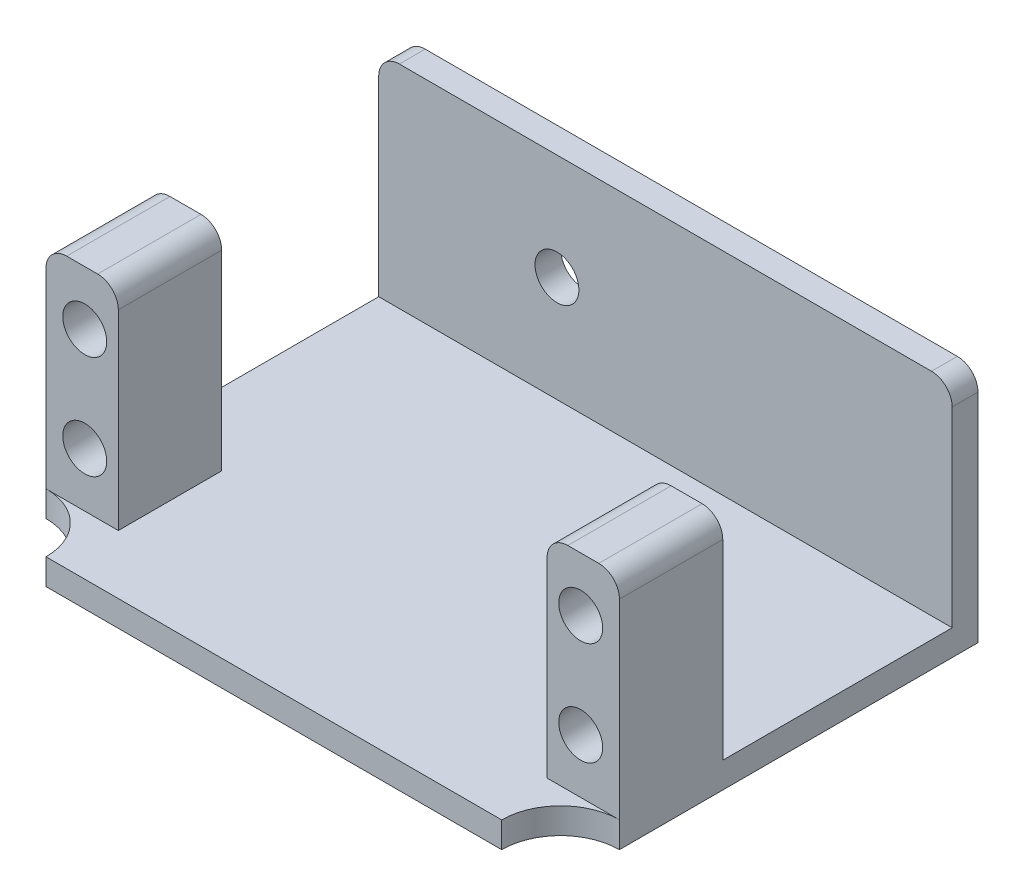
SolidWorks part; units mm, degrees
ref_plane "Front" through (0, 0, 0) normal (0, 0, 1) x (1, 0, 0)
ref_plane "Top" through (0, 0, 0) normal (0, 1, 0) x (1, 0, 0)
ref_plane "Right" through (0, 0, 0) normal (1, 0, 0) x (0, 0, -1)
sketch "Sketch1" plane through (0, 0, 0) normal (0, 1, 0) x (1, 0, 0)
  line L1 (0, 0) -> (55.5, 0)
  line L2 (0, 0) -> (0, 37.9)
  line L3 (0, 37.9) -> (55.5, 37.9)
  line L4 (55.5, 0) -> (55.5, 37.9)
  dimension "D1" = 37.9
  dimension "D2" = 55.5
extrude "bracketBase" add sketch "Sketch1" along normal blind 2.5
ref_plane "referencePlane1" through (0, 0, -8.2) normal (0, 0, 1) x (1, 0, 0)
sketch "Sketch2" plane through (0, 0, -8.2) normal (0, 0, 1) x (1, 0, 0)
  line L0 (27.75, 2.5) -> (27.75, 23) construction
  line L1 (0, 2.5) -> (7, 2.5)
  line L2 (0, 2.5) -> (0, 23)
  line L3 (0, 23) -> (7, 23)
  line L4 (7, 2.5) -> (7, 23)
  line L5 (0, 2.5) -> (55.5, 2.5) construction
  line L6 (55.5, 23) -> (48.5, 23)
  line L7 (48.5, 2.5) -> (48.5, 23)
  line L8 (55.5, 2.5) -> (48.5, 2.5)
  line L9 (55.5, 2.5) -> (55.5, 23)
  dimension "D1" = 20.5
  dimension "D2" = 7
extrude "servoMountingHoleTabs" add sketch "Sketch2" along normal blind 2.5
sketch "Sketch3" plane through (0, 0, -5.7) normal (0, 0, 1) x (1, 0, 0)
  line L0 (0, 12.75) -> (7, 12.75) construction
  line L3 (0, 23) -> (0, 2.5) construction
  line L4 (7, 2.5) -> (7, 23) construction
  line L5 (7, 23) -> (0, 23) construction
  line L6 (27.75, 2.5) -> (27.75, 23) construction
  line L7 (0, 2.5) -> (55.5, 2.5) construction
  circle A0 centre (3.75, 17.75) radius 2.125
  circle A1 centre (3.75, 7.75) radius 2.125
  circle A2 centre (51.75, 7.75) radius 2.125
  circle A3 centre (51.75, 17.75) radius 2.125
  dimension "D1" = 4.25
  dimension "D2" = 3.75
  dimension "D3" = 5.25
extrude "servoMountingHoles" cut sketch "Sketch3" against normal blind 2.5
sketch "Sketch4" plane through (0, 0, 0) normal (0, 1, 0) x (1, 0, 0)
  line L0 (55.5, 8.2) -> (55.5, 37.9) construction
  line L1 (0, 37.9) -> (55.5, 37.9)
  line L2 (0, 37.9) -> (0, 40.4)
  line L3 (0, 40.4) -> (55.5, 40.4)
  line L4 (55.5, 37.9) -> (55.5, 40.4)
  dimension "D1" = 2.5
extrude "baseWall" add sketch "Sketch4" along normal up to surface (23 mm away) up to face at (3.5, 23, -6.95)
sketch "Sketch6" plane through (0, 2.5, 0) normal (0, 1, 0) x (1, 0, 0)
  circle A0 centre (0, 0) radius 5.7
  circle A1 centre (55.5, 0) radius 5.7
extrude "baseTrim" cut sketch "Sketch6" against normal blind 2.5
fillet "Fillet1" radius 2 6 edges at (7, 23, -6.95) (48.5, 23, -6.95) (0, 23, -6.95) (55.5, 23, -6.95) (55.5, 23, -39.15) (0, 23, -39.15)
sketch "Sketch7" plane through (0, 0, -40.4) normal (0, 0, -1) x (-1, 0, 0)
  line L0 (0, 21) -> (0, 0) construction
  line L1 (-55.5, 0) -> (0, 0) construction
  circle A0 centre (-17.25, 12.75) radius 2.125
  dimension "D1" = 4.25
  dimension "D2" = 17.25
  dimension "D3" = 12.75
extrude "M4mountingHole" cut sketch "Sketch7" against normal blind 10
sketch "Sketch8" plane through (0, 0, -8.2) normal (0, 0, -1) x (-1, 0, 0)
  line L4 (-48.5, 2.5) -> (-48.5, 21)
  line L5 (-50.5, 23) -> (-53.5, 23)
  line L6 (-55.5, 21) -> (-55.5, 2.5)
  line L7 (-55.5, 2.5) -> (-48.5, 2.5)
  line L8 (-48.5, 2.5) -> (-48.5, 21)
  line L9 (-50.5, 23) -> (-53.5, 23)
  line L10 (-55.5, 21) -> (-55.5, 2.5)
  line L11 (-55.5, 2.5) -> (-48.5, 2.5)
  line L12 (-2, 23) -> (-5, 23)
  line L13 (-7, 21) -> (-7, 2.5)
  line L14 (-7, 2.5) -> (0, 2.5)
  line L15 (0, 2.5) -> (0, 21)
  line L16 (-2, 23) -> (-5, 23)
  line L17 (-7, 21) -> (-7, 2.5)
  line L18 (-7, 2.5) -> (0, 2.5)
  line L19 (0, 2.5) -> (0, 21)
  circle A0 centre (-51.75, 17.75) radius 2.125 construction
  circle A1 centre (-51.75, 17.75) radius 2.125
  arc A2 (-48.5, 21) -> (-50.5, 23) centre (-50.5, 21) ccw
  arc A3 (-53.5, 23) -> (-55.5, 21) centre (-53.5, 21) ccw
  arc A4 (-48.5, 21) -> (-50.5, 23) centre (-50.5, 21) ccw
  arc A5 (-53.5, 23) -> (-55.5, 21) centre (-53.5, 21) ccw
  arc A6 (-5, 23) -> (-7, 21) centre (-5, 21) ccw
  arc A7 (0, 21) -> (-2, 23) centre (-2, 21) ccw
  arc A8 (-5, 23) -> (-7, 21) centre (-5, 21) ccw
  arc A9 (0, 21) -> (-2, 23) centre (-2, 21) ccw
  circle A10 centre (-51.75, 7.75) radius 2.125 construction
  circle A11 centre (-51.75, 7.75) radius 2.125
  circle A12 centre (-3.75, 17.75) radius 2.125 construction
  circle A13 centre (-3.75, 17.75) radius 2.125
  circle A14 centre (-3.75, 7.75) radius 2.125 construction
  circle A15 centre (-3.75, 7.75) radius 2.125
  dimension "D1" = 0
  dimension "D2" = 0
extrude "Boss-Extrude1" add sketch "Sketch8" along normal blind 7.5
